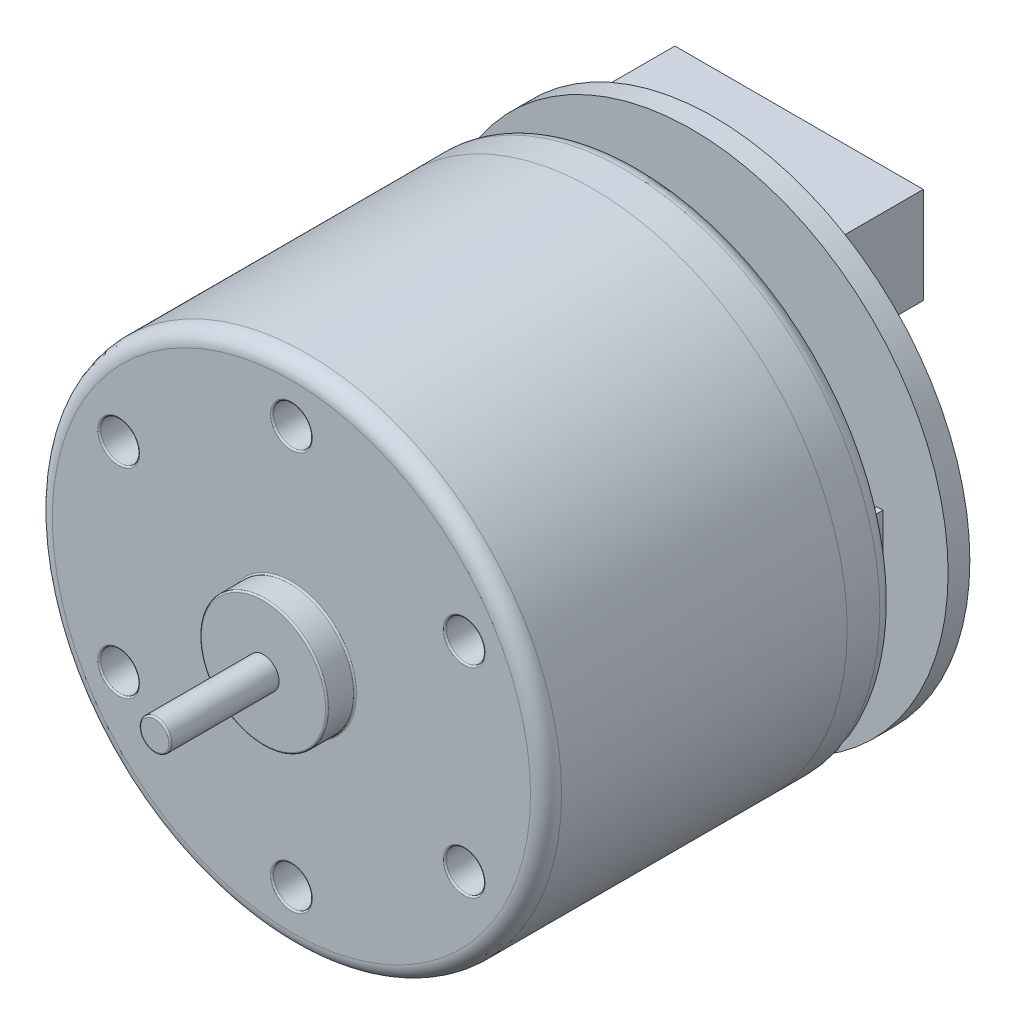
SolidWorks part; units mm, degrees
ref_plane "Front Plane" through (0, 0, 0) normal (0, 0, 1) x (1, 0, 0)
ref_plane "Top Plane" through (0, 0, 0) normal (0, 1, 0) x (1, 0, 0)
ref_plane "Right Plane" through (0, 0, 0) normal (1, 0, 0) x (0, 0, -1)
sketch "Sketch1" plane through (0, 0, 0) normal (0, 0, 1) x (1, 0, 0)
  line L1 (0, 12.85) -> (-11.1284, 6.425) construction
  line L2 (-11.1284, 6.425) -> (-11.1284, -6.425) construction
  line L3 (-11.1284, -6.425) -> (0, -12.85) construction
  line L4 (0, -12.85) -> (11.1284, -6.425) construction
  line L5 (11.1284, -6.425) -> (11.1284, 6.425) construction
  line L6 (11.1284, 6.425) -> (0, 12.85) construction
  circle A0 centre (0, 0) radius 16.4
  circle A1 centre (0, 0) radius 12.85 construction
  circle A2 centre (0, 0) radius 11.1284 construction
  circle A3 centre (0, 12.85) radius 1.25
  circle A4 centre (-11.1284, 6.425) radius 1.25
  circle A5 centre (11.1284, 6.425) radius 1.25
  circle A6 centre (11.1284, -6.425) radius 1.25
  circle A7 centre (0, -12.85) radius 1.25
  circle A8 centre (-11.1284, -6.425) radius 1.25
  circle A9 centre (0, 0) radius 4.1
  circle A10 centre (0, 0) radius 1
  dimension "D1" = 32.8
  dimension "D2" = 25.7
  dimension "D3" = 2.5
  dimension "D4" = 8.2
  dimension "D5" = 2
extrude "Boss-Extrude1" add sketch "Sketch1" against normal blind 19.4 contours A8 | A7 | A6 | A5 | A3 | A4 | A0 A8 A7 A6 A5 A4 A3 | A9 A10 | A10 region at (-15.9361, 0, 0) region at (0, 12.85, 0) region at (-11.1284, 6.425, 0) region at (11.1284, 6.425, 0) region at (11.1284, -6.425, 0) region at (0, -12.85, 0) region at (-11.1284, -6.425, 0) region at (-3.984, 0, 0) region at (0, 0, 0)
ref_plane "Plane1" through (0, 0, -27.2) normal (0, 0, 1) x (1, 0, 0)
sketch "Sketch3" plane through (0, 0, -27.2) normal (0, 0, 1) x (1, 0, 0)
  circle A0 centre (0, 0) radius 16.5
  dimension "D1" = 33
extrude "Boss-Extrude3" add sketch "Sketch3" along normal blind 1.4 separate body
sketch "Sketch4" plane through (0, 0, -27.2) normal (0, 0, 1) x (1, 0, 0)
  line L0 (-16.4, 0) -> (16.4, 0) construction
  line L1 (0, 16.4) -> (0, -16.4) construction
  line L2 (12.3, -1.4) -> (11.9, -1.4)
  line L3 (12.3, -1.4) -> (12.3, 1.4)
  line L4 (12.3, 1.4) -> (11.9, 1.4)
  line L5 (11.9, -1.4) -> (11.9, 1.4)
  line L6 (12.3, -1.4) -> (11.9, 1.4) construction
  line L7 (12.3, 1.4) -> (11.9, -1.4) construction
  line L8 (-12.3, 1.4) -> (-11.9, 1.4)
  line L9 (-11.9, -1.4) -> (-11.9, 1.4)
  line L10 (-12.3, -1.4) -> (-11.9, -1.4)
  line L11 (-12.3, -1.4) -> (-12.3, 1.4)
  circle A0 centre (0, 0) radius 16.4 construction
  point P5 (12.1, 0)
  dimension "D1" = 2.8
  dimension "D2" = 0.4
  dimension "D3" = 4.1
extrude "Boss-Extrude4" add sketch "Sketch4" along normal blind 4.6 and the other way blind 1.1
extrude "Boss-Extrude5" add sketch "Sketch1<3>" along normal blind 1.8 contours A9 A10 | A10 region at (-3.984, 0, 0) region at (0, 0, 0)
sketch "Sketch1<3>" plane through (0, 0, 0) normal (0, 0, 1) x (1, 0, 0) same geometry as "Sketch1"
extrude "Boss-Extrude6" add sketch "Sketch1<4>" along normal blind 8.8 and the other way blind 32 contours A10 region at (0, 0, 0)
sketch "Sketch1<4>" plane through (0, 0, 0) normal (0, 0, 1) x (1, 0, 0) same geometry as "Sketch1"
extrude "Cut-Extrude1" cut sketch "Sketch1<5>" against normal blind 2 contours A5 | A6 | A7 | A8 | A4 | A3 region at (0, 12.85, 0) region at (-11.1284, 6.425, 0) region at (11.1284, 6.425, 0) region at (11.1284, -6.425, 0) region at (0, -12.85, 0) region at (-11.1284, -6.425, 0)
sketch "Sketch1<5>" plane through (0, 0, 0) normal (0, 0, 1) x (1, 0, 0) same geometry as "Sketch1"
ref_plane "Plane2" through (0, 0, -33.4) normal (0, 0, 1) x (1, 0, 0)
sketch "Sketch5" plane through (0, 0, -33.4) normal (0, 0, 1) x (1, 0, 0)
  circle A0 centre (0, 0) radius 6.7
  circle A1 centre (0, 0) radius 1 construction
  circle A2 centre (0, 0) radius 1
  dimension "D1" = 13.4
extrude "Boss-Extrude7" add sketch "Sketch5" along normal blind 4.2
sketch "Sketch6" plane through (0, 0, -27.2) normal (0, 0, 1) x (1, 0, 0)
  line L0 (0, 16.5) -> (0, -16.5) construction
  line L2 (8, 13.7) -> (-8, 13.7)
  line L3 (8, 13.7) -> (8, 7.5)
  line L4 (8, 7.5) -> (-8, 7.5)
  line L5 (-8, 13.7) -> (-8, 7.5)
  line L6 (8, 13.7) -> (-8, 7.5) construction
  line L7 (8, 7.5) -> (-8, 13.7) construction
  circle A0 centre (0, 0) radius 16.5 construction
  point P5 (0, 10.6)
  point P10 (-8, 10.6)
  dimension "D1" = 16
  dimension "D2" = 6.2
  dimension "D3" = 2.8
extrude "Boss-Extrude8" add sketch "Sketch6" against normal blind 5.5
sketch "Sketch2" plane through (0, 0, -19.4) normal (0, 0, -1) x (-1, 0, 0)
  circle A0 centre (0, 0) radius 16.4 construction
  circle A1 centre (0, 0) radius 16.4
extrude "Boss-Extrude9" add sketch "Sketch2" along normal blind 3.1 separate body
fillet "Fillet1" radius 0.1 11 edges at (6.7, 0, -29.2) (6.7, 0, -33.4) (4.1, 0, 0) (4.1, 0, 1.8) (12.3784, 6.425, 0) (12.3784, -6.425, 0) (1.25, -12.85, 0) (-9.8784, -6.425, 0) (-9.8784, 6.425, 0) (1.25, 12.85, 0) (1, 0, 8.8)
fillet "Fillet2" radius 1 5 edges at (-12.1, -1.4, -28.3) (-12.1, 1.4, -28.3) (12.1, -1.4, -28.3) (12.1, 1.4, -28.3) (16.4, 0, 0)
fillet "Fillet3" radius 1 1 edges at (-16.4, 0, -22.5)
